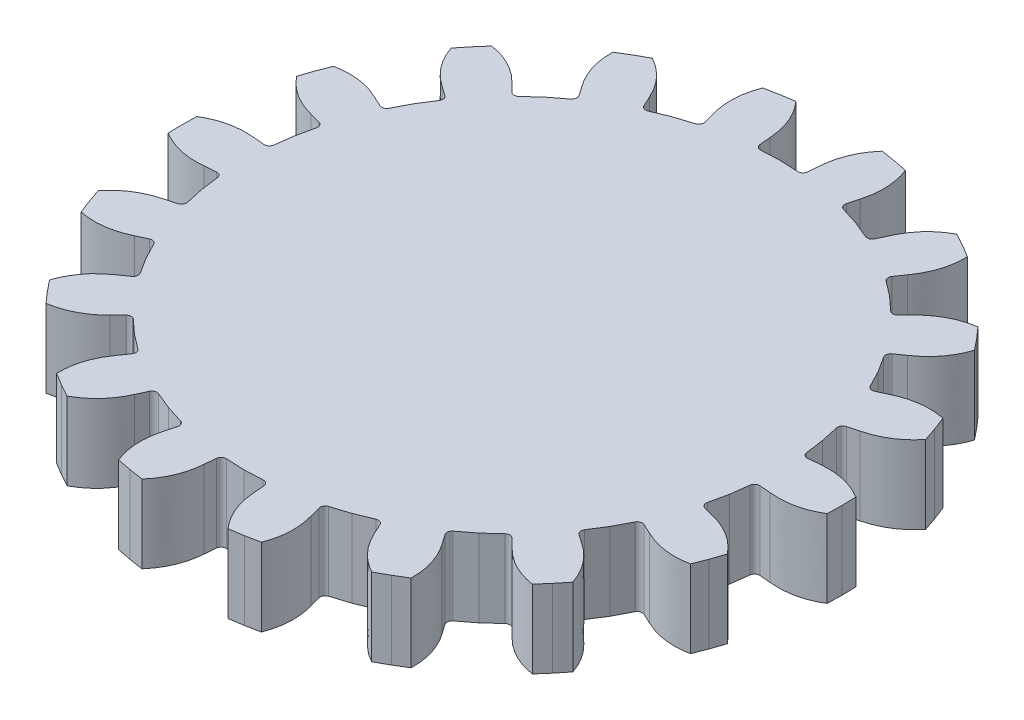
SolidWorks part; units mm, degrees
ref_plane "Front Plane" through (0, 0, 0) normal (0, 0, 1) x (1, 0, 0)
ref_plane "Top Plane" through (0, 0, 0) normal (0, 1, 0) x (1, 0, 0)
ref_plane "Right Plane" through (0, 0, 0) normal (1, 0, 0) x (0, 0, -1)
sketch "Sketch2" plane through (0, 0, 0) normal (0, 1, 0) x (1, 0, 0)
  line L0 (0, 0) -> (-45.4276, 0) construction
  line L1 (0, 0) -> (-44.5139, 1.9435) construction
  line L2 (0, 0) -> (-43.3229, 3.7903) construction
  line L3 (0, 0) -> (-25.445, 4.4866) construction
  line L4 (-25.7392, 2.2519) -> (-27.2858, 2.3872)
  line L5 (-25.7392, 2.2519) -> (-25.445, 4.4866)
  line L6 (-25.445, 4.4866) -> (0, 0)
  line L7 (-31.7697, 1.3871) -> (-31.8, 0)
  line L8 (-25.445, -4.4866) -> (0, 0)
  line L9 (-25.7392, -2.2519) -> (-25.445, -4.4866)
  line L10 (-25.7392, -2.2519) -> (-27.2858, -2.3872)
  line L11 (-31.7697, -1.3871) -> (-31.8, 0)
  circle A0 centre (0, 0) radius 25.8375 construction
  circle A1 centre (0, 0) radius 27.39 construction
  circle A2 centre (0, 0) radius 31.8 construction
  spline S0 degree 2 poles (-27.2858, 2.3872) (-29.7333, 2.6318) (-31.7697, 1.3871) knots 0 0 0 1 1 1
  spline S1 degree 2 poles (-27.2858, -2.3872) (-29.7333, -2.6318) (-31.7697, -1.3871) knots 0 0 0 1 1 1
  point P19 (-30.2868, 2.0783)
  dimension "D1" = 63.6
  dimension "D2" = 54.78
  dimension "D3" = 51.675
  dimension "D4" = 2.5
  dimension "D5" = 10
  dimension "D6" = 5
extrude "Boss-Extrude1" add sketch "Sketch2" along normal blind 7.5
fillet "Fillet1" radius 0.5 2 edges at (-25.7392, 3.75, -2.2519) (-25.7392, 3.75, 2.2519)
pattern_circular "CirPattern1" count 18 over 360 about axis through (0, 7.5, 0) along (0, -1, 0) of "Boss-Extrude1", "Fillet1" reverse direction yes
